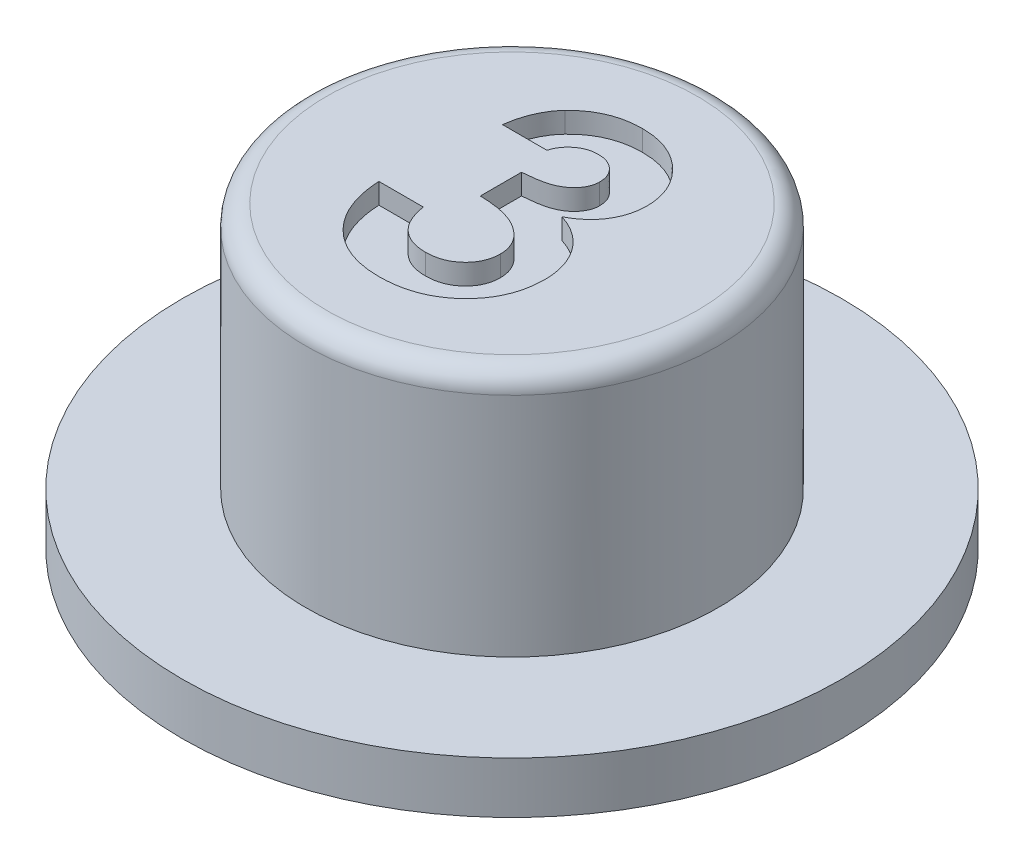
SolidWorks part; units mm, degrees
ref_plane "Front Plane" through (0, 0, 0) normal (0, 0, 1) x (1, 0, 0)
ref_plane "Top Plane" through (0, 0, 0) normal (0, 1, 0) x (1, 0, 0)
ref_plane "Right Plane" through (0, 0, 0) normal (1, 0, 0) x (0, 0, -1)
sketch "Sketch1" plane through (0, 0, 0) normal (0, 0, 1) x (1, 0, 0)
  line L1 (0, 7.25) -> (5, 7.25)
  line L2 (5, 7.25) -> (5, 1.25)
  line L3 (5, 1.25) -> (8, 1.25)
  line L4 (8, 1.25) -> (8, 0)
  line L6 (0, 7.25) -> (0, 6.9292) construction
  line L7 (0, 7.25) -> (0, 0)
  line L10 (0, 0) -> (8, 0)
  dimension "D1" = 5
  dimension "D2" = 3
  dimension "D3" = 6
  dimension "D4" = 1.25
revolve "Revolve1" add sketch "Sketch1" angle 360 about L6
sketch "Sketch2" plane through (0, 0, 0) normal (0, -1, 0) x (1, 0, 0)
  line L1 (-1.25, -1.75) -> (1.25, -1.75)
  line L2 (-1.25, -1.75) -> (-1.25, 1.75)
  line L3 (-1.25, 1.75) -> (1.25, 1.75)
  line L4 (1.25, -1.75) -> (1.25, 1.75)
  line L5 (-1.25, -1.75) -> (1.25, 1.75) construction
  line L6 (-1.25, 1.75) -> (1.25, -1.75) construction
  point P0 (0, 0)
  dimension "D1" = 2.5
  dimension "D2" = 3.5
extrude "Cut-Extrude1" cut sketch "Sketch2" against normal blind 3.5 contours L3 L4 L1 L2
fillet "Fillet1" radius 0.5 1 edges at (-5, 7.25, 0)
sketch "Sketch3" plane through (0, 7.25, 0) normal (0, 1, 0) x (1, 0, 0)
  line L0 (-3.3541, -3) -> (3.3541, -3) construction
  line L1 (0, 0) -> (0, -3) construction
  circle A0 centre (0, 0) radius 4.5 construction
  text T0 "3" font "Century Gothic" height 6
  dimension "D1" = 3
extrude "Cut-Extrude2" cut sketch "Sketch3" against normal blind 0.5
